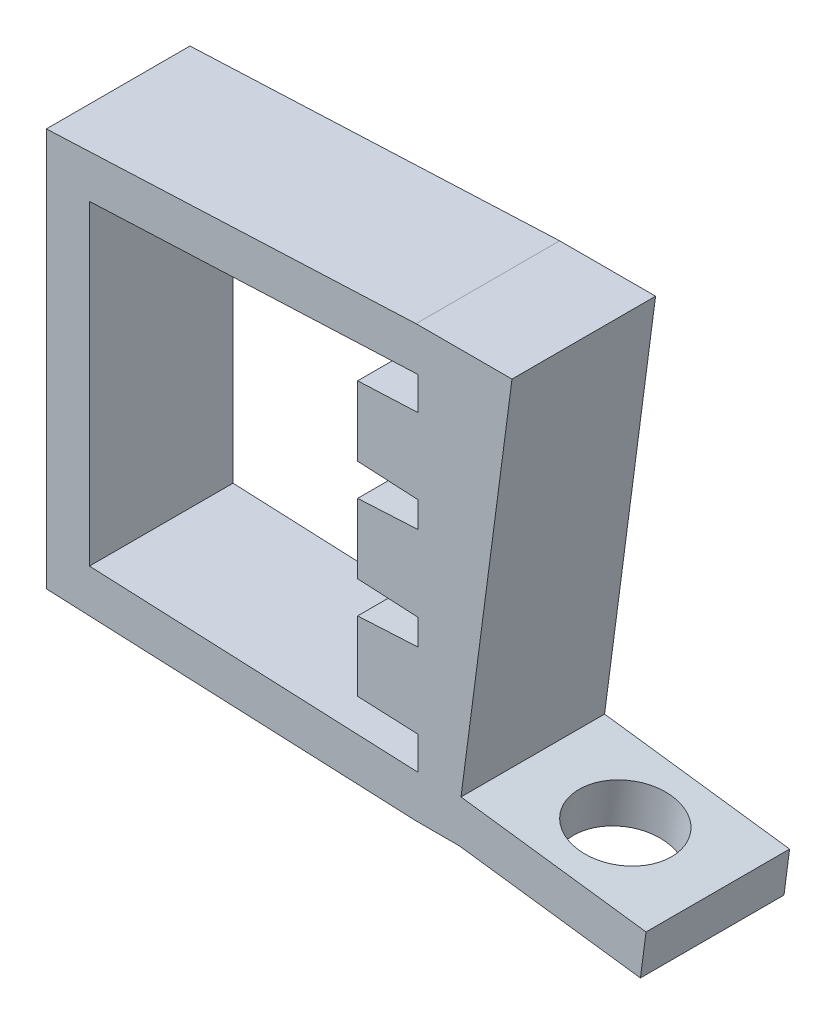
SolidWorks part; units mm, degrees
ref_plane "Top" through (0, 0, 0) normal (0, 0, 1) x (1, 0, 0)
ref_plane "Front" through (0, 0, 0) normal (0, 1, 0) x (1, 0, 0)
ref_plane "Right" through (0, 0, 0) normal (1, 0, 0) x (0, 0, -1)
sketch "Sketch1" plane through (0, 0, 0) normal (0, 0, 1) x (1, 0, 0)
  line L0 (0, 0) -> (22.8782, -0.9989)
  line L1 (-3, -2.8719) -> (22.7473, -3.996)
  line L2 (0, 0) -> (0, 22)
  line L3 (0, 22) -> (22.8782, 22.9989)
  line L4 (-3, -2.8719) -> (-3, 24.8719)
  line L5 (-3, 24.8719) -> (22.7473, 25.996)
  line L9 (22.8782, -0.9989) -> (22.8782, 1.3011)
  line L10 (22.8782, 1.3011) -> (18.6782, 1.4845)
  line L11 (18.6782, 1.4845) -> (18.6782, 6.3347)
  line L12 (18.6782, 6.3347) -> (22.8782, 6.5548)
  line L13 (22.8782, 6.5548) -> (22.8782, 8.3548)
  line L14 (22.8782, 8.3548) -> (18.6782, 8.5749)
  line L15 (18.6782, 8.5749) -> (18.6782, 13.4251)
  line L19 (25.7473, -3.996) -> (22.7473, -3.996)
  line L20 (22.8782, 22.9989) -> (22.8782, 20.6989)
  line L21 (22.8782, 20.6989) -> (18.6782, 20.5155)
  line L22 (18.6782, 20.5155) -> (18.6782, 15.6653)
  line L23 (18.6782, 15.6653) -> (22.8782, 15.4452)
  line L24 (22.8782, 15.4452) -> (22.8782, 13.6452)
  line L25 (22.8782, 13.6452) -> (18.6782, 13.4251)
  line L26 (25.7473, -3.996) -> (38.3754, -5.6585)
  line L27 (38.3754, -5.6585) -> (38.767, -2.6842)
  line L28 (38.767, -2.6842) -> (25.8782, -0.9874)
  line L29 (25.8782, -0.9874) -> (29.4306, 25.996)
  line L30 (29.4306, 25.996) -> (22.7473, 25.996)
  dimension "D1" = 92.5
  dimension "D2" = 92.5
  dimension "D3" = 22
  dimension "D4" = 22.9
  dimension "D6" = 90
  dimension "D7" = 3
  dimension "D8" = 92.5
  dimension "D9" = 93
  dimension "D10" = 93
  dimension "D11" = 1.8
  dimension "D12" = 2.3
  dimension "D13" = 3
  dimension "D14" = 13
  dimension "D15" = 82.5
  dimension "D16" = 2.3
  dimension "D17" = 1.8
  dimension "D18" = 3
  dimension "D19" = 4.2
  dimension "D5" = 3
extrude "Boss-Extrude1" add sketch "Sketch1" along normal blind 10
sketch "Sketch2" plane through (-2.9766, -0.2145, 0) normal (0.1305, 0.9914, 0) x (0.9914, -0.1305, 0)
  line L3 (28.9718, 0) -> (41.7088, 0) construction
  line L4 (41.7088, -10) -> (41.7088, 0) construction
  circle A1 centre (35.2088, -5) radius 3.25
  point P4 (0, 0)
  dimension "D3" = 6.5
  dimension "D1" = 5
  dimension "D2" = 6.5
extrude "Cut-Extrude1" cut sketch "Sketch2" along normal blind 10
